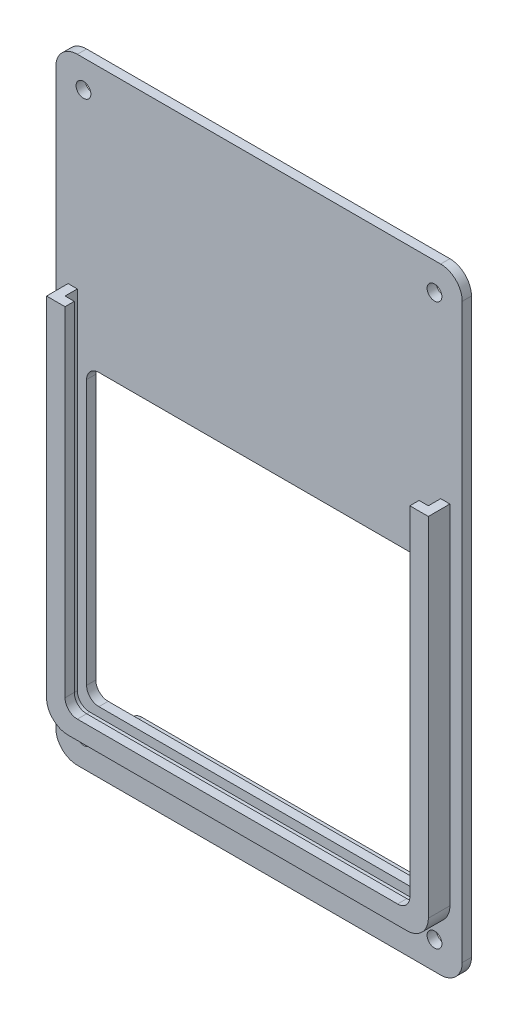
SolidWorks part; units mm, degrees
material "ABS"
ref_plane "Спереди" through (0, 0, 0) normal (0, 0, 1) x (1, 0, 0)
ref_plane "Сверху" through (0, 0, 0) normal (0, 1, 0) x (1, 0, 0)
ref_plane "Справа" through (0, 0, 0) normal (1, 0, 0) x (0, 0, -1)
sketch "Эскиз1" plane through (0, 0, 0) normal (0, 0, 1) x (1, 0, 0)
  line L1 (-33, -50) -> (33, -50)
  line L2 (-33, -50) -> (-33, 50)
  line L3 (-33, 50) -> (33, 50)
  line L4 (33, -50) -> (33, 50)
  line L5 (-33, -50) -> (33, 50) construction
  line L6 (-33, 50) -> (33, -50) construction
  point P0 (0, 0)
  dimension "D1" = 100
  dimension "D2" = 66
extrude "Бобышка-Вытянуть1" add sketch "Эскиз1" along normal blind 1.5 contours L2 L3 L4 L1
fillet "Скругление1" radius 3.5 4 edges at (-33, -50, 0.75) (33, -50, 0.75) (33, 50, 0.75) (-33, 50, 0.75)
sketch "Эскиз2" plane through (0, 0, 1.5) normal (0, 0, 1) x (1, 0, 0)
  line L0 (-29.5, -50) -> (29.5, -50) construction
  line L1 (-33, -50) -> (-24, -50)
  line L2 (-33, -50) -> (-33, -41)
  line L3 (-33, -41) -> (-24, -41)
  line L4 (-24, -50) -> (-24, -41)
  line L5 (33, -50) -> (24, -50)
  line L6 (33, -50) -> (33, -41)
  line L7 (33, -41) -> (24, -41)
  line L8 (24, -50) -> (24, -41)
  line L9 (-28, 7) -> (28, 7)
  line L10 (-28, 7) -> (-28, -40)
  line L11 (-28, -40) -> (28, -40)
  line L12 (28, 7) -> (28, -40)
  line L13 (-33, -46.5) -> (-33, 46.5) construction
  line L14 (33, -46.5) -> (33, 46.5) construction
  dimension "D1" = 57
  dimension "D2" = 5
  dimension "D3" = 5
  dimension "D4" = 10
  dimension "D5" = 9
extrude "Вырез-Вытянуть1" cut sketch "Эскиз2" against normal blind 1.5 contours L12 L9 L10 L3 L4 L11 L8 L7 region at (0, -16.5, 1.5)
fillet "Скругление2" radius 2 4 edges at (-28, -40, 0.75) (28, -40, 0.75) (-28, 7, 0.75) (28, 7, 0.75)
sketch "Эскиз3" plane through (0, 0, 1.5) normal (0, 0, 1) x (1, 0, 0)
  line L0 (-26, 7) -> (26, 7) construction
  line L1 (-28, -40) -> (28, -40)
  line L2 (-28, -40) -> (-28, 7)
  line L3 (-28, 7) -> (28, 7)
  line L4 (28, -40) -> (28, 7)
  line L5 (-29.5, -41.5) -> (29.5, -41.5)
  line L6 (-29.5, -41.5) -> (-29.5, 17)
  line L7 (-29.5, 17) -> (29.5, 17)
  line L8 (29.5, -41.5) -> (29.5, 17)
  line L10 (-26, -40) -> (26, -40) construction
  line L11 (28, 5) -> (28, -38) construction
  line L12 (-28, 5) -> (-28, -38) construction
  line L14 (-31, 17) -> (31, 17)
  line L15 (-31, 17) -> (-31, -43)
  line L16 (-31, -43) -> (31, -43)
  line L17 (31, 17) -> (31, -43)
  dimension "D1" = 1.5
  dimension "D2" = 1.5
  dimension "D3" = 1.5
  dimension "D4" = 10
  dimension "D5" = 1.5
  dimension "D6" = 1.5
  dimension "D7" = 1.5
extrude "Бобышка-Вытянуть2" add sketch "Эскиз3" along normal blind 2 contours L17 L14 L8 L5 L6 L15 L16 region at (0, -42.3628, 1.5)
fillet "Скругление3" radius 2 2 edges at (29.5, -41.5, 2.5) (-29.5, -41.5, 2.5)
sketch "Эскиз4" plane through (0, 0, 3.5) normal (0, 0, 1) x (1, 0, 0)
  line L0 (-28, 5) -> (-28, -38) construction
  line L1 (-31, -43) -> (31, -43)
  line L2 (-31, -43) -> (-31, 17)
  line L3 (-31, 17) -> (31, 17)
  line L4 (31, -43) -> (31, 17)
  line L5 (-28, 17) -> (28, 17)
  line L6 (-28, 17) -> (-28, -40)
  line L7 (-28, -40) -> (28, -40)
  line L8 (28, 17) -> (28, -40)
  line L9 (-26, -40) -> (26, -40) construction
  line L10 (28, 5) -> (28, -38) construction
  line M4 (31, -43) -> (31, 17)
  line M5 (31, 17) -> (29.5, 17)
  line M6 (29.5, 17) -> (29.5, -39.5)
  arc M7 (29.5, -39.5) -> (27.5, -41.5) centre (27.5, -39.5) cw
  line M8 (27.5, -41.5) -> (-27.5, -41.5)
  arc M9 (-27.5, -41.5) -> (-29.5, -39.5) centre (-27.5, -39.5) cw
  line M10 (-29.5, -39.5) -> (-29.5, 17)
  line M11 (-29.5, 17) -> (-31, 17)
  line M12 (-31, 17) -> (-31, -43)
  line M13 (-31, -43) -> (31, -43)
extrude "Бобышка-Вытянуть3" add sketch "Эскиз4" along normal blind 1.5 contours M13 M4 M5 M6 M7 M8 M9 M10 M11 M12 | L3 L8 L7 L6 M10 M9 M8 M7 M6 region at (-30.1372, -13, 3.5) region at (-28.75, 16.1691, 3.5)
fillet "Скругление4" radius 2 2 edges at (-28, -40, 4.25) (28, -40, 4.25)
fillet "Скругление5" radius 3.5 2 edges at (-31, -43, 3.25) (31, -43, 3.25)
sketch "Эскиз5" plane through (0, 0, 0) normal (0, 0, -1) x (-1, 0, 0)
  line L1 (-24, -41) -> (24, -41)
  line L2 (-24, -41) -> (-24, -48.5)
  line L3 (-24, -48.5) -> (24, -48.5)
  line L4 (24, -41) -> (24, -48.5)
  line L5 (-31.5, 48.5) -> (31.5, 48.5)
  line L6 (-31.5, 48.5) -> (-31.5, 8)
  line L7 (-31.5, 8) -> (31.5, 8)
  line L8 (31.5, 48.5) -> (31.5, 8)
  line L9 (31.5, 48.5) -> (24, 48.5)
  line L10 (31.5, 48.5) -> (31.5, 41)
  line L11 (31.5, 41) -> (24, 41)
  line L12 (24, 48.5) -> (24, 41)
  line L13 (-31.5, 48.5) -> (-24, 48.5)
  line L14 (-31.5, 48.5) -> (-31.5, 41)
  line L15 (-31.5, 41) -> (-24, 41)
  line L16 (-24, 48.5) -> (-24, 41)
  line L18 (-33, -46.5) -> (-33, 46.5) construction
  line L19 (29.5, 50) -> (-29.5, 50) construction
  line L20 (29.5, -50) -> (-29.5, -50) construction
  dimension "D1" = 7.5
  dimension "D2" = 40.5
  dimension "D3" = 63
  dimension "D4" = 1.5
  dimension "D5" = 1.5
  dimension "D6" = 7.5
  dimension "D7" = 48
  dimension "D8" = 1.5
  dimension "D9" = 9
extrude "Бобышка-Вытянуть4" add sketch "Эскиз5" along normal blind 1.5 contours L5 L16 L15 L6 L7 L8 L11 L12 | L4 L1 L2 L3 region at (0, -44.75, 0) region at (0, 27.4889, 0)
fillet "Скругление6" radius 2 12 edges at (24, 41, -0.75) (24, 48.5, -0.75) (31.5, 41, -0.75) (31.5, 8, -0.75) (-31.5, 8, -0.75) (-31.5, 41, -0.75) (-24, 41, -0.75) (-24, 48.5, -0.75) (-24, -48.5, -0.75) (-24, -41, -0.75) (24, -41, -0.75) (24, -48.5, -0.75)
sketch "Эскиз6" plane through (0, 0, 1.5) normal (0, 0, 1) x (1, 0, 0)
  line L1 (-29.5, 50) -> (29.5, 50) construction
  line L2 (-33, -46.5) -> (-33, 46.5) construction
  line L3 (33, -46.5) -> (33, 46.5) construction
  line L4 (-29.5, -50) -> (29.5, -50) construction
  point P0 (-28.5, 45.5)
  point P1 (28.5, 45.5)
  point P3 (-28.5, -45.5)
  point P4 (28.5, -45.5)
  dimension "D1" = 4.5
  dimension "D2" = 4.5
  dimension "D3" = 4.5
  dimension "D4" = 4.5
hole_wizard "Отверстие с зазором M21" positions "Эскиз7" profile "Эскиз8" hole size "M2" standard "DIN" end condition through all
sketch "Эскиз7" plane through (0, 0, 1.5) normal (0, 0, 1) x (1, 0, 0)
  point P0 (-28.5, 45.5)
  point P3 (28.5, 45.5)
  point P6 (28.5, -45.5)
  point P9 (-28.5, -45.5)
sketch "Эскиз8" plane through (-28.5, 45.5, 1.5) normal (1, 0, 0) x (0, -1, 0)
  line L0 (0, 0) -> (0, 3)
  line L1 (0, 3) -> (1.2, 3)
  line L2 (1.2, 3) -> (1.2, 0)
  line L5 (1.2, 0) -> (0, 0)
  line L11 (0, -6.35) -> (0, 107.95) construction
  dimension "Диаметр сквозного отверстия" = 2.4
  dimension "Глубина сквозного отверстия" = 3
